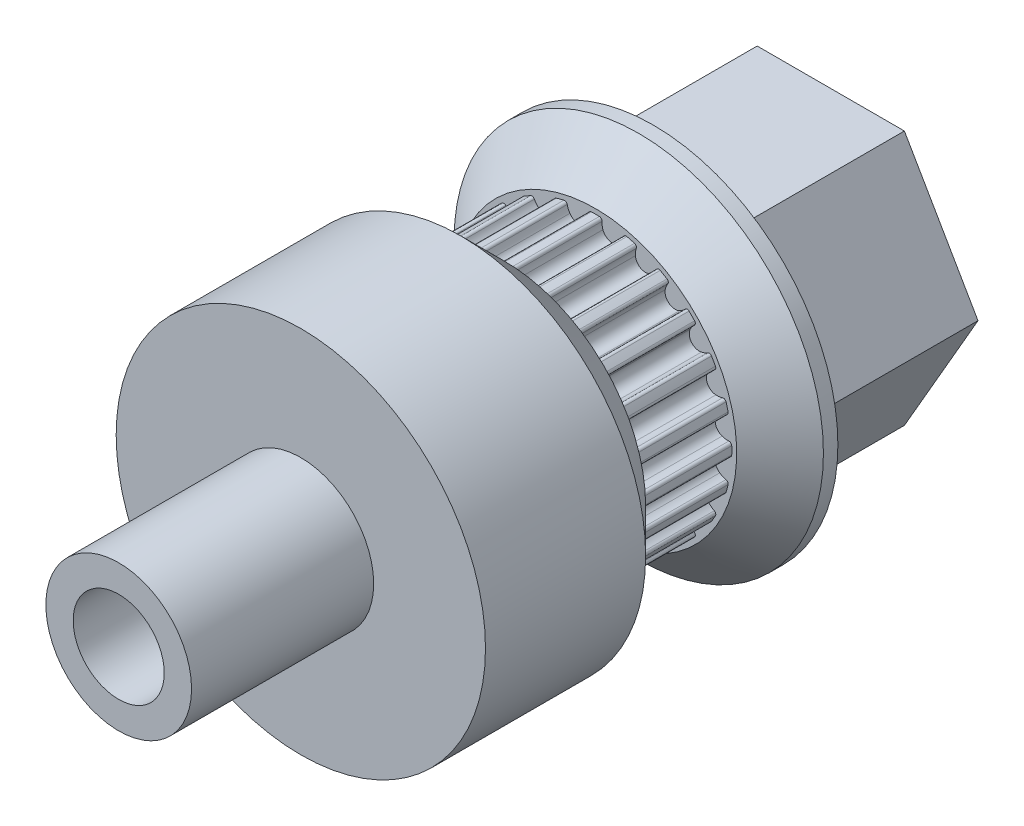
SolidWorks part; units mm, degrees
ref_plane "Front" through (0, 0, 0) normal (0, 0, 1) x (1, 0, 0)
ref_plane "Top" through (0, 0, 0) normal (0, 1, 0) x (1, 0, 0)
ref_plane "Right" through (0, 0, 0) normal (1, 0, 0) x (0, 0, -1)
ref_axis "CENTRAL AXIS" through (0, 0, 0) along (0, 0, 1)
sketch "Sketch1" plane through (0, 0, 0) normal (0, 0, 1) x (1, 0, 0)
  circle A0 centre (0, 0) radius 7.6394
  dimension "D1" = 15.2789
extrude "BASE" add sketch "Sketch1" along normal mid plane 5
sketch "Sketch2" plane through (0, 0, 2.5) normal (0, 0, 1) x (1, 0, 0)
  line L0 (0, 0) -> (0, 7.6394) construction
  line L1 (0.9971, 7.5741) -> (0, 0) construction
  line L2 (1.3922, 7.5115) -> (1.361, 7.2744) construction
  line L3 (0, 7.4894) -> (0, 7.6394)
  line L4 (1.9384, 7.2342) -> (1.9772, 7.3791)
  circle A0 centre (0, 0) radius 7.6394 construction
  arc A1 (0, 7.4894) -> (0.217, 7.4863) centre (0, 0) cw
  arc A2 (0.217, 7.4863) -> (0.3624, 7.3283) centre (0.2126, 7.3364) cw
  arc A3 (0.3624, 7.3283) -> (0.4129, 6.9564) centre (1.361, 7.2744) ccw
  arc A4 (0.4129, 6.9564) -> (1.4016, 6.8262) centre (0.9391, 7.1329) ccw
  arc A5 (0.9971, 7.5741) -> (1.3922, 7.5115) centre (0, 0) cw construction
  arc A6 (0, 7.6394) -> (1.9772, 7.3791) centre (0, 0) cw
  arc A7 (1.5466, 7.1724) -> (1.4016, 6.8262) centre (0.5682, 7.3788) cw
  arc A8 (1.728, 7.2874) -> (1.5466, 7.1724) centre (1.6934, 7.1414) ccw
  arc A9 (1.9384, 7.2342) -> (1.728, 7.2874) centre (0, 0) ccw
  dimension "D3" = 0.15
  dimension "D4" = 1
  dimension "D6" = 0.555
  dimension "D1" = 0.15
  dimension "D5" = 7.5
  dimension "D7" = 1
  dimension "D2" = 0.4
extrude "TOOTH PROFILE" cut sketch "Sketch2" against normal through all
pattern_circular "TEETH PATTERN" count 24 over 360 about axis through (0, 0, 2.5) along (0, 0, 1) of "TOOTH PROFILE"
sketch "Sketch3" plane through (0, 0, 2.5) normal (0, 0, 1) x (1, 0, 0)
  circle A0 centre (0, 0) radius 10.1394
  dimension "D1" = 20.2789
extrude "FLANGE" add sketch "Sketch3" along normal blind 3.175
mirror "FLANGE MIRROR" about plane through (0, 0, 0) normal (0, 0, 1) of "FLANGE"
chamfer "FLANGE CHAMFER" distance 2.3813 angle 45 2 edges at (10.1394, 0, -2.5) (10.1394, 0, 2.5)
sketch "Sketch4" [suppressed] plane through (0, 0, 7.675) normal (0, 0, 1) x (1, 0, 0)
  line L1 (2.823, -4.8895) -> (5.6459, 0)
  line L2 (5.6459, 0) -> (2.823, 4.8895)
  line L3 (2.823, 4.8895) -> (-2.823, 4.8895)
  line L4 (-2.823, 4.8895) -> (-5.6459, 0)
  line L5 (-5.6459, 0) -> (-2.823, -4.8895)
  line L6 (-2.823, -4.8895) -> (2.823, -4.8895)
  circle A0 centre (0, 0) radius 4.8895 construction
  dimension "D1" = 9.779
extrude "0.375 HEX BORE" [suppressed] cut sketch "Sketch4" against normal through all
chamfer "Chamfer2" [suppressed] distance 0.7937 angle 45
sketch "Sketch7" [suppressed] plane through (0, 0, 7.675) normal (0, 0, 1) x (1, 0, 0)
  line L1 (3.7395, -6.477) -> (7.479, 0)
  line L2 (7.479, 0) -> (3.7395, 6.477)
  line L3 (3.7395, 6.477) -> (-3.7395, 6.477)
  line L4 (-3.7395, 6.477) -> (-7.479, 0)
  line L5 (-7.479, 0) -> (-3.7395, -6.477)
  line L6 (-3.7395, -6.477) -> (3.7395, -6.477)
  circle A0 centre (0, 0) radius 6.477 construction
  dimension "D1" = 12.954
extrude "0.5 HEX BORE" [suppressed] cut sketch "Sketch7" against normal through all
chamfer "Chamfer3" [suppressed] distance 0.7937 angle 45
sketch "Sketch8" [suppressed] plane through (0, 0, -7.675) normal (0, 0, -1) x (-1, 0, 0)
  circle A0 centre (0, 0) radius 11.2395
  dimension "D1" = 22.479
extrude "Cut-Extrude6" [suppressed] cut sketch "Sketch8" against normal blind 5.6134
mirror "BEARING BORE MIRROR" [suppressed] about plane through (0, 0, 0) normal (0, 0, 1)
sketch "Sketch9" [suppressed] plane through (0, 0, -2.0616) normal (0, 0, -1) x (-1, 0, 0)
  circle A0 centre (0, 0) radius 7.9375
  dimension "D1" = 15.875
extrude "0.875 THRU HOLE" [suppressed] cut sketch "Sketch9" against normal through all
chamfer "Chamfer4" [suppressed] distance 0.7937 angle 45
sketch "Sketch10" [suppressed] plane through (0, 0, -7.675) normal (0, 0, -1) x (-1, 0, 0)
  circle A0 centre (0, 0) radius 14.4145
  dimension "D1" = 28.829
extrude "BORE" [suppressed] cut sketch "Sketch10" against normal blind 6.35
mirror "BORE MIRROR" [suppressed] about plane through (0, 0, 0) normal (0, 0, 1)
sketch "Sketch11" [suppressed] plane through (0, 0, -1.325) normal (0, 0, -1) x (-1, 0, 0)
  circle A0 centre (0, 0) radius 11.1125
  dimension "D1" = 22.225
extrude "THRU HOLE" [suppressed] cut sketch "Sketch11" against normal through all
chamfer "Chamfer5" [suppressed] distance 0.7937 angle 45
sketch "Sketch5" plane through (0, 0, 5.675) normal (0, 0, 1) x (1, 0, 0)
  circle A0 centre (0, 0) radius 9.3457 construction
  circle A1 centre (0, 0) radius 10.1394 construction
  text T0 "24T GT2" font "@HYSWLongFangSong" height 3.175
  dimension "D1" = 0.7937
extrude "ETCH SIDE 1" cut sketch "Sketch5" against normal blind 1
sketch "Sketch6" plane through (0, 0, -5.675) normal (0, 0, -1) x (-1, 0, 0)
  line L0 (0, 9.3457) -> (0, 0) construction
  circle A0 centre (0, 0) radius 9.3457 construction
  circle A2 centre (0, 0) radius 10.1394 construction
  text T0 "24T GT2" font "@HYSWLongFangSong" height 3.175
  dimension "D1" = 0.7937
extrude "ETCH SIDE 2" cut sketch "Sketch6" against normal blind 1
sketch "Sketch12" plane through (0, 0, -5.675) normal (0, 0, -1) x (-1, 0, 0)
  line L1 (5.15, 0) -> (2.575, 4.46)
  line L2 (2.575, 4.46) -> (-2.575, 4.46)
  line L3 (-2.575, 4.46) -> (-5.15, 0)
  line L4 (-5.15, 0) -> (-2.575, -4.46)
  line L5 (-2.575, -4.46) -> (2.575, -4.46)
  line L6 (2.575, -4.46) -> (5.15, 0)
  circle A0 centre (0, 0) radius 4.46 construction
  circle A1 centre (0, 0) radius 5.15 construction
  dimension "D1" = 10.3
extrude "Extrude-Thin1" add sketch "Sketch12" along normal blind 9.75 thin thin type one direction wall 2.54
sketch "Sketch14" plane through (0, 0, 5.675) normal (0, 0, 1) x (1, 0, 0)
  circle A0 centre (0, 0) radius 10.1394 construction
  circle A1 centre (0, 0) radius 10.1394
extrude "Boss-Extrude2" add sketch "Sketch14" along normal blind 8
sketch "Sketch15" plane through (0, 0, 13.675) normal (0, 0, 1) x (1, 0, 0)
  circle A0 centre (0, 0) radius 4
  circle A1 centre (0, 0) radius 2.5
  dimension "D1" = 8
  dimension "D2" = 5
extrude "Boss-Extrude3" add sketch "Sketch15" along normal blind 10
sketch "Sketch16" plane through (0, 0, 13.675) normal (0, 0, 1) x (1, 0, 0)
  circle A0 centre (0, 0) radius 1.7
  dimension "D1" = 3.4
extrude "Cut-Extrude7" cut sketch "Sketch16" against normal blind 30.828
equation "\"n\"= 24"
equation "\"p\"= 2mm"
equation "\"pd\"= \"n\" * \"p\" / pi"
equation "\"D1@Sketch1\"=\"pd\""
equation "\"D5@Sketch2\"=180/\"n\""
equation "\"D1@TEETH PATTERN\" = \"n\""
equation "\"w\"= 5mm"
equation "\"D1@BASE\" = \"w\""
equation "\"D1@Sketch3\"=\"pd\"+5mm"
